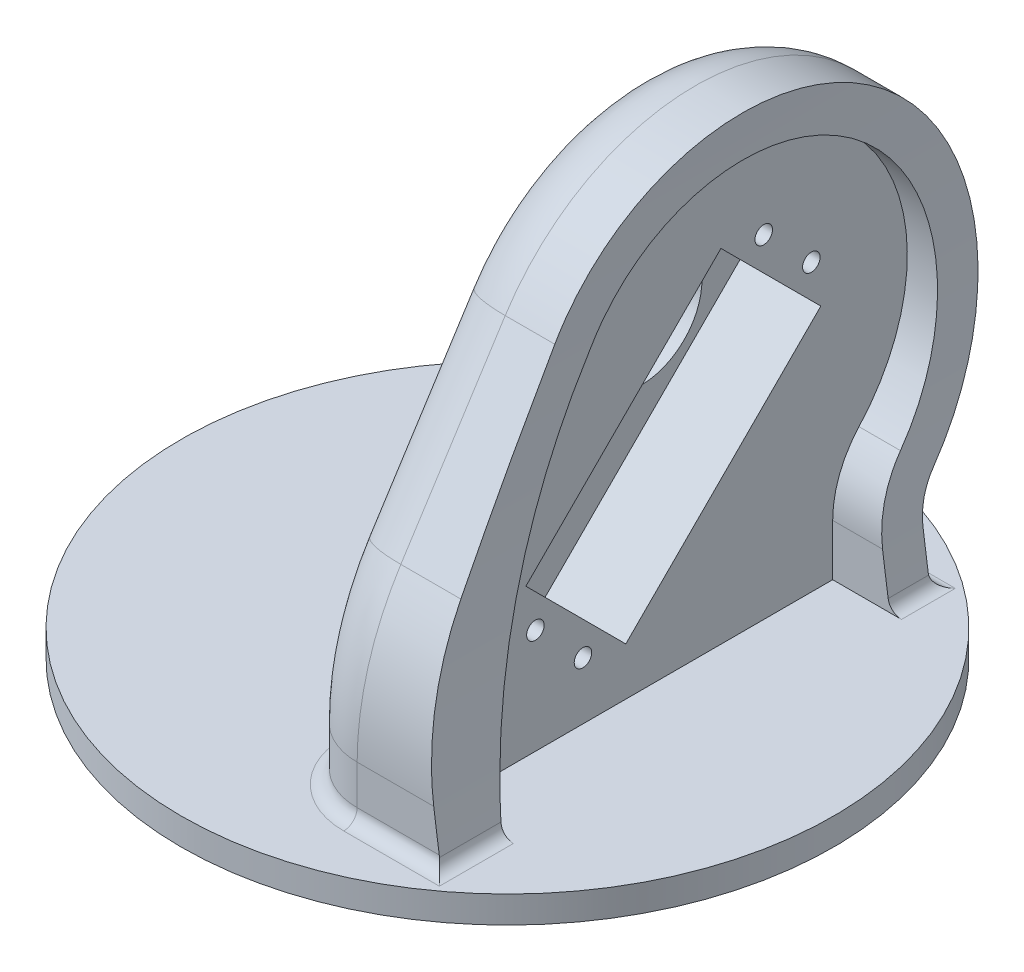
SolidWorks part; units mm, degrees
ref_plane "Front Plane" through (0, 0, 0) normal (0, 0, 1) x (1, 0, 0)
ref_plane "Top Plane" through (0, 0, 0) normal (0, 1, 0) x (1, 0, 0)
ref_plane "Right Plane" through (0, 0, 0) normal (1, 0, 0) x (0, 0, -1)
sketch "Sketch1" plane through (0, 0, 0) normal (0, 1, 0) x (1, 0, 0)
  line L0 (0, 7.25) -> (0, -7.25) construction
  circle A0 centre (0, 0) radius 48.5
  circle A1 centre (0, 7.25) radius 1.5
  circle A2 centre (0, -7.25) radius 1.5
  point P6 (0, 0)
  dimension "D1" = 14.5
  dimension "D2" = 97
  dimension "D3" = 3
  dimension "D4" = 3
extrude "Boss-Extrude1" add sketch "Sketch1" along normal blind 4
sketch "Sketch2" plane through (0, 0, 0) normal (0, -1, 0) x (1, 0, 0)
  circle A0 centre (0, 0) radius 3.75
  dimension "D1" = 7.5
extrude "Cut-Extrude1" cut sketch "Sketch2" against normal blind 1.5
sketch "Sketch3" plane through (0, 0, 0) normal (1, 0, 0) x (0, 0, -1)
  line L0 (30.34, 4) -> (-30.34, 4)
  line L1 (48.5, 4) -> (-48.5, 4) construction
  line L2 (30.34, 4) -> (30.34, 11.64)
  line L3 (-30.34, 4) -> (-30.34, 11.86)
  line L4 (-24.7927, 30.8361) -> (-9.2781, 55.1041)
  arc A0 (30.34, 11.64) -> (34.2527, 21.7431) centre (45.34, 11.64) cw
  arc A1 (34.2527, 21.7431) -> (-9.2781, 55.1041) centre (13.91, 40.28) ccw
  arc A2 (-30.34, 11.86) -> (-24.7927, 30.8361) centre (4.89, 11.86) cw
  circle A3 centre (13.91, 40.28) radius 9
  point P5 (0, 4)
  dimension "D3" = 15
  dimension "D5" = 35.23
  dimension "D6" = 18
  dimension "D1" = 60.68
  dimension "D2" = 7.64
  dimension "D4" = 7.86
  dimension "D7" = 13.91
  dimension "D8" = 40.28
extrude "Boss-Extrude2" add sketch "Sketch3" along normal blind 14 from offset 4
sketch "Sketch4" plane through (0, 0, 0) normal (1, 0, 0) x (0, 0, -1)
  line L0 (-0.41, 11.11) -> (28.5814, 40.1014)
  line L1 (-0.41, 11.11) -> (-15.2592, 25.9592)
  line L2 (28.5814, 40.1014) -> (13.7321, 54.9506)
  line L3 (-15.2592, 25.9592) -> (13.7321, 54.9506)
  line L4 (-30.34, 4) -> (30.34, 4) construction
  line L5 (-0.7636, 40.4549) -> (14.0857, 25.6057) construction
  line L6 (6.6611, 33.0303) -> (23.6316, 50.0009) construction
  line L7 (27.1672, 46.4653) -> (20.0961, 53.5364) construction
  circle A0 centre (27.1672, 46.4653) radius 1.3
  circle A1 centre (20.0961, 53.5364) radius 1.3
  circle A2 centre (-13.845, 19.5953) radius 1.3
  circle A3 centre (-6.774, 12.5242) radius 1.3
  point P15 (23.6316, 50.0009)
  dimension "D8" = 2.6
  dimension "D1" = 0.41
  dimension "D2" = 11.11
  dimension "D3" = 21
  dimension "D4" = 41
  dimension "D5" = 45
  dimension "D6" = 3.5
  dimension "D7" = 10
extrude "Cut-Extrude2" cut sketch "Sketch4" along normal through all from offset 6
sketch "Sketch7" plane through (18, 0, 0) normal (1, 0, 0) x (0, 0, -1)
  line L0 (33.34, 4) -> (33.34, 11.64) construction
  line L1 (-11.8057, 56.7201) -> (-27.3203, 32.452) construction
  line L2 (-33.34, 11.86) -> (-33.34, 4) construction
  line L3 (-33.34, 11.86) -> (-33.34, 4) construction
  line L4 (-30.34, 11.86) -> (-30.34, 4)
  line L5 (-30.34, 4) -> (30.34, 4)
  line L6 (30.34, 4) -> (30.34, 11.64)
  line L7 (-9.2781, 55.1041) -> (-24.7927, 30.8361)
  line L9 (-30.34, 4) -> (30.34, 4)
  line L10 (30.34, 4) -> (30.34, 11.64)
  line L13 (36.34, 4) -> (36.34, 11.64)
  line L14 (-14.3333, 58.336) -> (-29.8479, 34.0679)
  line L15 (-36.34, 11.86) -> (-36.34, 4)
  line L16 (-36.34, 4) -> (-27.34, 4)
  line L17 (30.34, 4) -> (36.34, 4)
  line L19 (-9.2781, 55.1041) -> (-24.7927, 30.8361) construction
  line L20 (-30.34, 11.86) -> (-30.34, 4) construction
  arc A0 (36.4702, 19.7225) -> (33.34, 11.64) centre (45.34, 11.64) ccw construction
  arc A1 (36.4702, 19.7225) -> (-11.8057, 56.7201) centre (13.91, 40.28) ccw construction
  arc A2 (-27.3203, 32.452) -> (-33.34, 11.86) centre (4.89, 11.86) ccw construction
  arc A3 (34.2527, 21.7431) -> (30.34, 11.64) centre (45.34, 11.64) ccw
  arc A4 (34.2527, 21.7431) -> (-9.2781, 55.1041) centre (13.91, 40.28) ccw
  arc A5 (-24.7927, 30.8361) -> (-30.34, 11.86) centre (4.89, 11.86) ccw
  arc A6 (34.2527, 21.7431) -> (30.34, 11.64) centre (45.34, 11.64) ccw
  arc A7 (34.2527, 21.7431) -> (-9.2781, 55.1041) centre (13.91, 40.28) ccw
  arc A9 (-27.3203, 32.452) -> (-33.34, 11.86) centre (4.89, 11.86) ccw construction
  arc A11 (38.6876, 17.7018) -> (36.34, 11.64) centre (45.34, 11.64) ccw
  arc A12 (38.6876, 17.7018) -> (-14.3333, 58.336) centre (13.91, 40.28) ccw
  arc A13 (-29.8479, 34.0679) -> (-36.34, 11.86) centre (4.89, 11.86) ccw
  arc A14 (-9.2781, 55.1041) -> (-27.34, 4) centre (72.447, -2.5241) ccw
  arc A15 (-24.7927, 30.8361) -> (-30.34, 11.86) centre (4.89, 11.86) ccw construction
  line M16 (-30.34, 11.86) -> (-30.34, 4)
  line M17 (-30.34, 4) -> (30.34, 4)
  line M18 (30.34, 4) -> (30.34, 11.64)
  arc M19 (30.34, 11.64) -> (34.2527, 21.7431) centre (45.34, 11.64) cw
  arc M20 (34.2527, 21.7431) -> (-9.2781, 55.1041) centre (13.91, 40.28) ccw
  line M21 (-9.2781, 55.1041) -> (-24.7927, 30.8361)
  arc M22 (-24.7927, 30.8361) -> (-30.34, 11.86) centre (4.89, 11.86) ccw
  dimension "D7" = 100
  dimension "D6" = 3
  dimension "D1" = 0
  dimension "D2" = 3
  dimension "D3" = 0
  dimension "D5" = 3
extrude "Boss-Extrude3" add sketch "Sketch7" along normal blind 9 and the other way up to surface (14 mm away) contours A14 L17 L13 A11 A12 L14 A13 L15 L16 M20 M19 M18 M16 M22 M21 | A14 M21 M22 M16 M17 region at (18, 20.5833, 26.1371) region at (18, 7.93, 31.4304) other way up to face at (4, 23.3781, -2.2919)
sketch "Sketch8" plane through (0, 0, 0) normal (0, 0, 1) x (1, 0, 0)
  line L0 (27, 73.8017) -> (21, 73.8017)
  line L1 (27, 73.8017) -> (4, 73.8017) construction
  line L2 (4, 4) -> (27, 4) construction
  line L3 (26.5, 4) -> (27, 4)
  line L4 (27, 4) -> (27, 73.8017)
  arc A0 (21, 73.8017) -> (26.5, 4) centre (520.9817, 78.08) ccw
  dimension "D3" = 500
  dimension "D1" = 6
  dimension "D2" = 0.5
extrude "Cut-Extrude3" cut sketch "Sketch8" against normal through all both and the other way through all
fillet "Fillet1" radius 10 6 edges at (4, 7.82, -36.34) (4, 14.8903, -36.9474) (4, 7.93, 36.34) (4, 23.4287, 34.6837) (4, 46.2019, 22.0906) (4, 66.8867, -34.3008)
fillet "Fillet2" radius 2 5 edges at (20.25, 4, 36.34) (6.9289, 4, 33.4111) (20.25, 4, -36.34) (6.9289, 4, -33.4111) (4, 4, 0)
fillet "Fillet3" radius 2 2 edges at (26.5, 4, -34.34) (26.5, 4, 32.84)
